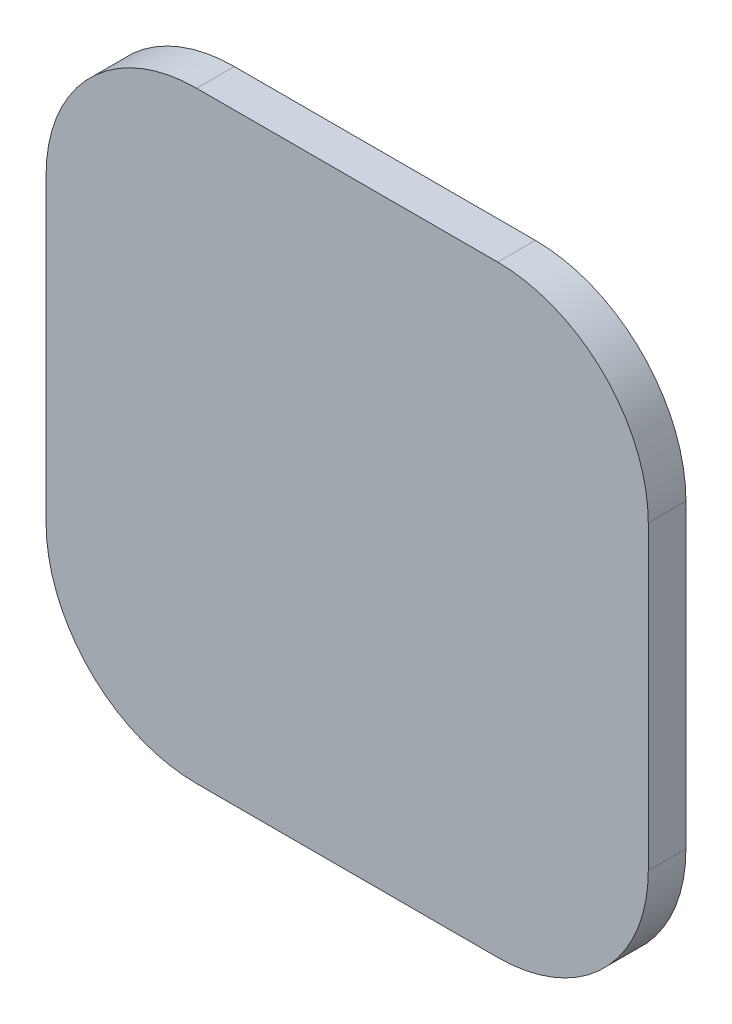
SolidWorks part; units mm, degrees
material "Custom Plastic"
ref_plane "Front Plane" through (0, 0, 0) normal (0, 0, 1) x (1, 0, 0)
ref_plane "Top Plane" through (0, 0, 0) normal (0, 1, 0) x (1, 0, 0)
ref_plane "Right Plane" through (0, 0, 0) normal (1, 0, 0) x (0, 0, -1)
sketch "Sketch1" plane through (0, 0, 0) normal (0, 0, 1) x (1, 0, 0)
  line L1 (-20, -40) -> (20, -40)
  line L2 (-40, -20) -> (-40, 20)
  line L3 (-20, 40) -> (20, 40)
  line L4 (40, -20) -> (40, 20)
  line L5 (-40, -40) -> (40, 40) construction
  line L6 (-40, 40) -> (40, -40) construction
  arc A0 (40, 20) -> (20, 40) centre (20, 20) ccw
  arc A1 (20, -40) -> (40, -20) centre (20, -20) ccw
  arc A2 (-20, -40) -> (-40, -20) centre (-20, -20) cw
  arc A3 (-40, 20) -> (-20, 40) centre (-20, 20) cw
  point P0 (0, 0)
  dimension "D3" = 20
  dimension "D4" = 20
  dimension "D5" = 20
  dimension "D6" = 20
  dimension "D1" = 80
  dimension "D2" = 80
extrude "Boss-Extrude1" add sketch "Sketch1" along normal blind 5
sketch "Sketch3" plane through (0, 0, 0) normal (0, 0, -1) x (-1, 0, 0)
  circle A0 centre (0, 0) radius 20
  dimension "D1" = 40
extrude "Cut-Extrude2" cut sketch "Sketch3" against normal blind 2
sketch "Sketch4" plane through (0, 0, 2) normal (0, 0, -1) x (-1, 0, 0)
  line L0 (-0.9978, 1.12) -> (-0.9978, -1.12)
  arc A0 (-0.9978, -1.12) -> (-0.9978, 1.12) centre (0, 0) ccw
  circle A1 centre (0, 0) radius 2.5
  dimension "D1" = 3
  dimension "D3" = 5
  dimension "D2" = 2.24
extrude "Boss-Extrude2" add sketch "Sketch4" along normal blind 7
fillet "Fillet1" radius 10 1 edges at (-2.5, 0, 2)
